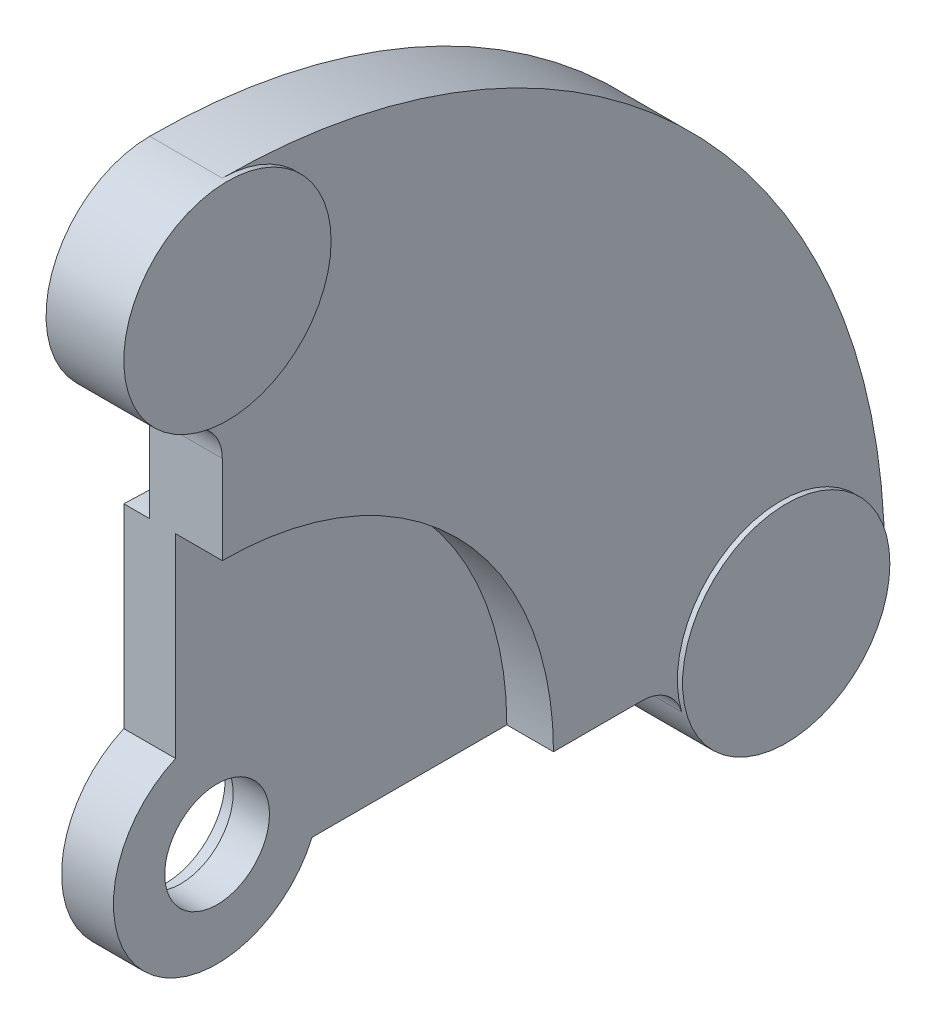
SolidWorks part; units mm, degrees
ref_plane "Alzado" through (0, 0, 0) normal (0, 0, 1) x (1, 0, 0)
ref_plane "Planta" through (0, 0, 0) normal (0, 1, 0) x (1, 0, 0)
ref_plane "Vista lateral" through (0, 0, 0) normal (1, 0, 0) x (0, 0, -1)
sketch "Croquis2" plane through (0, 0, 0) normal (1, 0, 0) x (0, 0, -1)
  line L0 (0, 43.9) -> (0, 0)
  line L1 (0, 0) -> (43.9, 0)
  arc A0 (63.9, 0) -> (0, 63.9) centre (0, 0) ccw
  circle A1 centre (0, 53.9) radius 10
  circle A2 centre (53.9, 0) radius 10
  arc A3 (31.95, 0) -> (0, 31.95) centre (0, 0) ccw
  dimension "D1" = 127.8
  dimension "D2" = 20
  dimension "D3" = 20
  dimension "D4" = 63.9
  dimension "D5" = 53.9
  dimension "D6" = 20
extrude "Saliente-Extruir1" add sketch "Croquis2" along normal mid plane 5 contours L1 A3 L0 region at (0, 13.56, -13.56)
extrude "Saliente-Extruir2" add sketch "Croquis2<3>" along normal blind 7 contours A3 L1 A2 A0 A1 L0 region at (0, 32.0258, -32.0258)
sketch "Croquis2<3>" plane through (0, 0, 0) normal (1, 0, 0) x (0, 0, -1) same geometry as "Croquis2"
extrude "Saliente-Extruir3" add sketch "Croquis2<4>" along normal blind 7.5 contours A1 | A2 region at (0, 53.9, 0) region at (0, 0, -53.9)
sketch "Croquis2<4>" plane through (0, 0, 0) normal (1, 0, 0) x (0, 0, -1) same geometry as "Croquis2"
fillet "Redondeo1" radius 4 1 edges at (0, 0, 0)
fillet "Redondeo2" radius 4 2 edges at (3.5, 0, -43.9) (3.5, 43.9, 0)
sketch "Croquis3" plane through (2.5, 0, 0) normal (1, 0, 0) x (0, 0, -1)
  circle A0 centre (4, 4) radius 10
  dimension "D1" = 20
extrude "Saliente-Extruir4" add sketch "Croquis3" against normal up to surface (5 mm away) up to face at (-2.5, 10.4347, -10.4347)
sketch "Croquis4" plane through (2.5, 0, 0) normal (1, 0, 0) x (0, 0, -1)
  circle A0 centre (4, 4) radius 5.05
  dimension "D1" = 10.1
extrude "Cortar-Extruir1" cut sketch "Croquis4" against normal blind 131
sketch "Croquis5" plane through (-2.5, 0, 0) normal (-1, 0, 0) x (0, 0, 1)
  circle A0 centre (-4, 4) radius 5.78
  dimension "D1" = 11.56
extrude "Cortar-Extruir2" cut sketch "Croquis5" against normal blind 1.5
